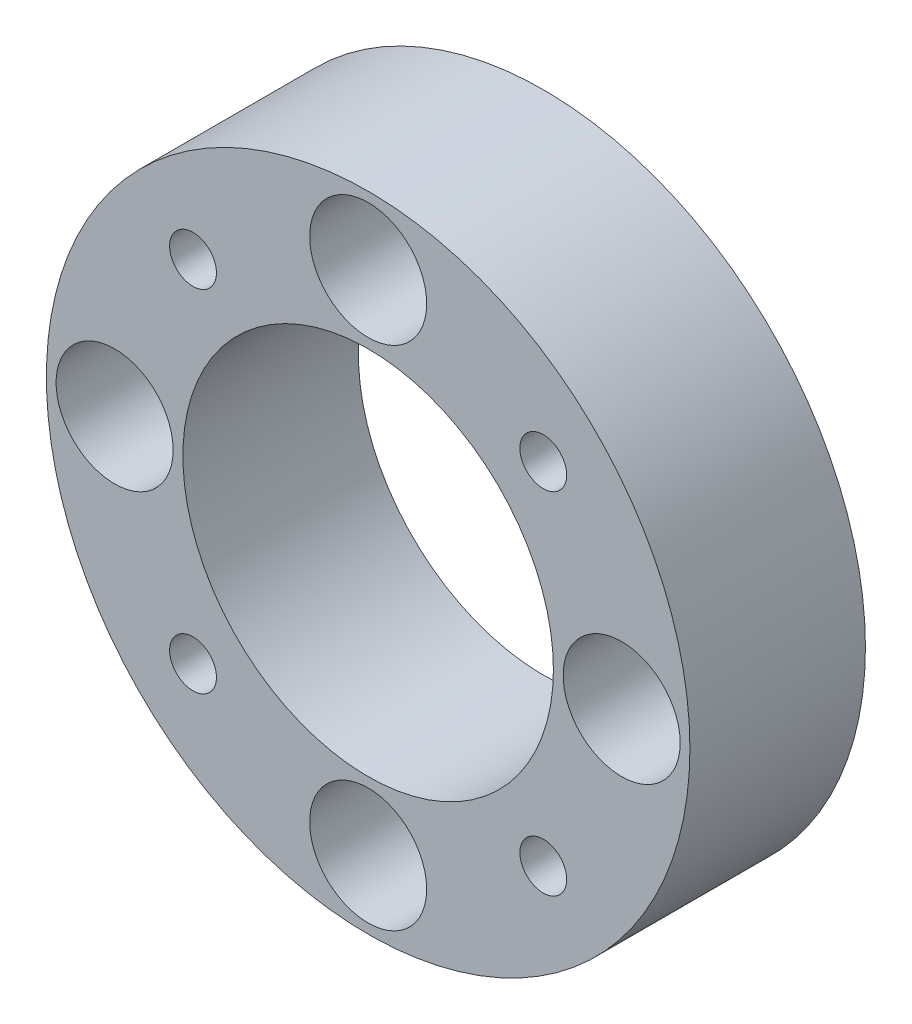
SolidWorks part; units mm, degrees
ref_plane "Front Plane" through (0, 0, 0) normal (0, 0, 1) x (1, 0, 0)
ref_plane "Top Plane" through (0, 0, 0) normal (0, 1, 0) x (1, 0, 0)
ref_plane "Right Plane" through (0, 0, 0) normal (1, 0, 0) x (0, 0, -1)
sketch "Sketch1" plane through (0, 0, 0) normal (0, 0, 1) x (1, 0, 0)
  line L0 (0, 0) -> (8.9803, 8.9803) construction
  circle A0 centre (0, 0) radius 12.7 construction
  circle A1 centre (8.9803, 8.9803) radius 1.2
  circle A2 centre (8.9803, -8.9803) radius 1.2
  circle A3 centre (-8.9803, -8.9803) radius 1.2
  circle A4 centre (-8.9803, 8.9803) radius 1.2
  circle A5 centre (0, 0) radius 9.5
  circle A6 centre (0, 0) radius 16.5
  circle A7 centre (0, 0) radius 13 construction
  circle A8 centre (0, 13) radius 1.55
  circle A9 centre (13, 0) radius 1.55
  circle A10 centre (0, -13) radius 1.55
  circle A11 centre (-13, 0) radius 1.55
  point P14 (0, 0)
  point P26 (0, 0)
  dimension "D1" = 4
  dimension "D2" = 4
extrude "Boss-Extrude1" add sketch "Sketch1" along normal blind 9
sketch "Sketch2" plane through (0, 0, 9) normal (0, 0, 1) x (1, 0, 0)
  circle A0 centre (0, 13) radius 3
  circle A1 centre (13, 0) radius 3
  circle A2 centre (0, -13) radius 3
  circle A3 centre (-13, 0) radius 3
  point P12 (0, 0)
  point P22 (0, 0)
  dimension "D1" = 4
extrude "Cut-Extrude1" cut sketch "Sketch2" against normal blind 6
